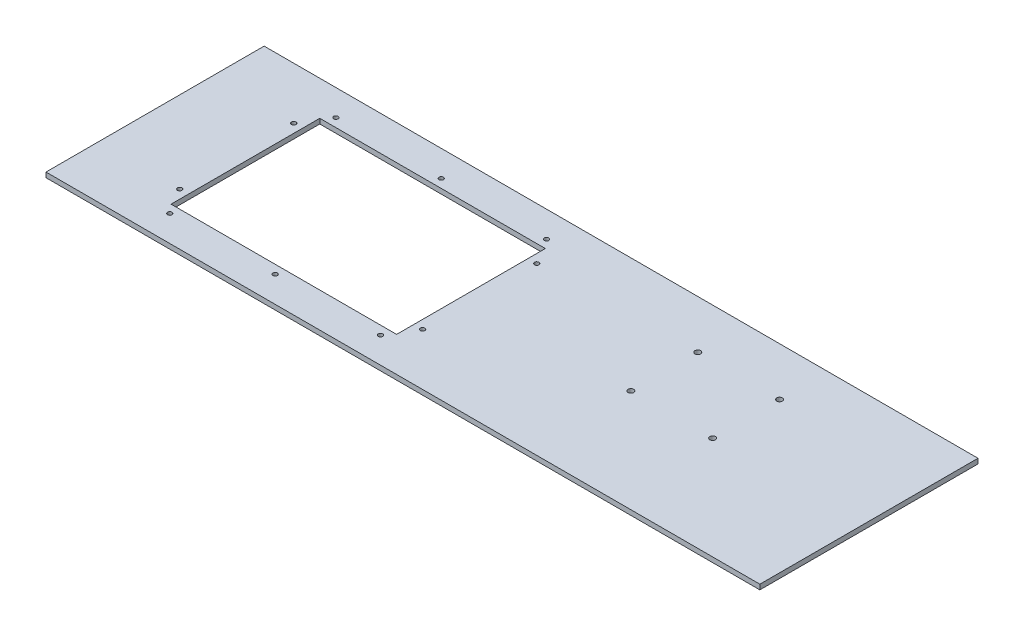
SolidWorks part; units mm, degrees
ref_plane "Ön Düzlem" through (0, 0, 0) normal (0, 0, 1) x (1, 0, 0)
ref_plane "Üst Düzlem" through (0, 0, 0) normal (0, 1, 0) x (1, 0, 0)
ref_plane "Sağ Düzlem" through (0, 0, 0) normal (1, 0, 0) x (0, 0, -1)
sketch "Çizim1" plane through (0, 0, 0) normal (0, 1, 0) x (1, 0, 0)
  line L1 (-720, -220) -> (720, -220)
  line L2 (-720, -220) -> (-720, 220)
  line L3 (-720, 220) -> (720, 220)
  line L4 (720, -220) -> (720, 220)
  line L5 (-720, -220) -> (720, 220) construction
  line L6 (-720, 220) -> (720, -220) construction
  point P0 (0, 0)
  dimension "D1" = 1440
  dimension "D2" = 440
base flange "Taban-Flanş1" sketch "Çizim1" thickness 10 reverse thickness direction no parameters "D1"=0.7366
sketch "Çizim2" plane through (0, -10, 0) normal (0, -1, 0) x (-1, 0, 0)
  line L0 (-720, 220) -> (720, 220) construction
  line L1 (537.75, 150) -> (82.75, 150)
  line L2 (537.75, 150) -> (537.75, -150)
  line L3 (537.75, -150) -> (82.75, -150)
  line L4 (82.75, 150) -> (82.75, -150)
  line L5 (720, 220) -> (720, -220) construction
  dimension "D1" = 70
  dimension "D2" = 182.25
  dimension "D3" = 300
  dimension "D4" = 455
extrude "Kes-Ekstrüzyon1" cut sketch "Çizim2" against normal blind 10 normal cut yes
sketch "Çizim3" plane through (0, -10, 0) normal (0, -1, 0) x (-1, 0, 0)
  line L0 (537.75, -150) -> (537.75, 150) construction
  line L1 (720, -220) -> (-720, -220) construction
  line L2 (82.75, -150) -> (537.75, -150) construction
  line L3 (82.75, 150) -> (82.75, -150) construction
  circle A0 centre (555.25, -115) radius 4.5
  circle A1 centre (522.75, -167.5) radius 4.5
  circle A2 centre (310.25, -167.5) radius 4.5
  circle A3 centre (97.75, -167.5) radius 4.5
  circle A4 centre (65.25, -115) radius 4.5
  dimension "D1" = 9
  dimension "D2" = 9
  dimension "D4" = 105
  dimension "D6" = 15
  dimension "D3" = 17.5
  dimension "D5" = 17.5
  dimension "D7" = 17.5
  dimension "D8" = 212.5
  dimension "D9" = 212.5
  dimension "D10" = 17.5
  dimension "D11" = 17.5
  dimension "D12" = 105
sketch "Çizim4" plane through (0, -10, 0) normal (0, -1, 0) x (-1, 0, 0)
  line L0 (537.75, -150) -> (537.75, 150) construction
  line L1 (82.75, -150) -> (537.75, -150) construction
  line L3 (82.75, 150) -> (82.75, -150) construction
  line L4 (720, -220) -> (-720, -220) construction
  line L5 (82.75, 0) -> (217.8041, 0) construction
  circle A0 centre (555.25, -115) radius 4.5
  circle A1 centre (522.75, -167.5) radius 4.5
  circle A2 centre (310.25, -167.5) radius 4.5
  circle A3 centre (97.75, -167.5) radius 4.5
  circle A4 centre (65.25, -115) radius 4.5
  circle A5 centre (65.25, 115) radius 4.5
  circle A6 centre (97.75, 167.5) radius 4.5
  circle A7 centre (310.25, 167.5) radius 4.5
  circle A8 centre (522.75, 167.5) radius 4.5
  circle A9 centre (555.25, 115) radius 4.5
  dimension "D1" = 9
  dimension "D2" = 17.5
  dimension "D3" = 35
  dimension "D4" = 17.5
  dimension "D5" = 15
  dimension "D6" = 17.5
  dimension "D7" = 212.5
  dimension "D8" = 17.5
  dimension "D9" = 212.5
  dimension "D10" = 17.5
  dimension "D11" = 105
extrude "Kes-Ekstrüzyon4" cut sketch "Çizim4" against normal blind 10 normal cut yes
sketch "Çizim5" plane through (0, 0, 0) normal (0, 1, 0) x (1, 0, 0)
  line L0 (720, 220) -> (-720, 220) construction
  line L1 (-720, -220) -> (720, -220) construction
  circle A0 centre (252.25, -12.5) radius 5.75
  circle A1 centre (252.25, 122.5) radius 5.75
  circle A2 centre (417.25, 122.5) radius 5.75
  circle A3 centre (417.25, -12.5) radius 5.75
  dimension "D1" = 11.5
  dimension "D2" = 165
  dimension "D3" = 97.5
  dimension "D4" = 207.5
  dimension "D5" = 165
extrude "Kes-Ekstrüzyon5" cut sketch "Çizim5" against normal blind 10 normal cut yes
sketch "Büküm-Çizgileri1" [suppressed] plane through (0, 0, 0) normal (0, 1, 0) x (1, 0, 0)
sketch "Sınırlandırma-Kutusu1" [suppressed] plane through (0, 0, 0) normal (0, 1, 0) x (1, 0, 0)
sheet metal parameters "Sac-Levha1" thickness 10 parameters "D1"=0.7366
flat pattern "Düz-Çoğaltma1" [suppressed]
sketch "Büküm-Çizgileri2" plane through (0, 0, 0) normal (0, 1, 0) x (1, 0, 0)
sketch3d "Sınırlandırma-Kutusu2" [suppressed]
  line L0 (-720, 220, 0) -> (720, 220, 0) construction
  line L1 (-720, -220, 0) -> (720, -220, 0) construction
  line L2 (-720, 220, 0) -> (-720, -220, 0) construction
  line L3 (720, 220, 0) -> (720, -220, 0) construction
sheet metal parameters "Sac-Levha2" thickness 10 parameters "D1"=0.7366
flat pattern "Düz-Çoğaltma1"
sketch "Büküm-Çizgileri2" plane through (0, 0, 0) normal (0, 1, 0) x (1, 0, 0)
sketch3d "Sınırlandırma-Kutusu2" [suppressed]
  line L0 (720, 220, 0) -> (-720, 220, 0) construction
  line L1 (720, -220, 0) -> (-720, -220, 0) construction
  line L2 (720, 220, 0) -> (720, -220, 0) construction
  line L3 (-720, 220, 0) -> (-720, -220, 0) construction
sheet metal parameters "Sac-Levha3" thickness 10 parameters "D1"=0.7366
flat pattern "Düz-Çoğaltma1" [suppressed]
sketch "Büküm-Çizgileri2" plane through (0, 0, 0) normal (0, 1, 0) x (1, 0, 0)
sketch3d "Sınırlandırma-Kutusu2" [suppressed]
  line L0 (720, 220, 0) -> (-720, 220, 0) construction
  line L1 (720, -220, 0) -> (-720, -220, 0) construction
  line L2 (720, 220, 0) -> (720, -220, 0) construction
  line L3 (-720, 220, 0) -> (-720, -220, 0) construction
sketch "Çizim3-1" [suppressed] plane through (0, -10, 0) normal (0, -1, 0) x (-1, 0, 0)
  line L0 (537.75, -150) -> (537.75, 150) construction
  line L1 (720, -220) -> (-720, -220) construction
  line L2 (82.75, -150) -> (537.75, -150) construction
  line L3 (82.75, 150) -> (82.75, -150) construction
  circle A0 centre (555.25, -115) radius 4.5
  circle A1 centre (522.75, -167.5) radius 4.5
  circle A2 centre (310.25, -167.5) radius 4.5
  circle A3 centre (97.75, -167.5) radius 4.5
  circle A4 centre (65.25, -115) radius 4.5
  dimension "D1" = 9
  dimension "D2" = 9
  dimension "D4" = 105
  dimension "D6" = 15
  dimension "D3" = 17.5
  dimension "D5" = 17.5
  dimension "D7" = 17.5
  dimension "D8" = 212.5
  dimension "D9" = 212.5
  dimension "D10" = 17.5
  dimension "D11" = 17.5
  dimension "D12" = 105
sheet metal parameters "Sac-Levha4" thickness 10 parameters "D1"=0.7366
flat pattern "Düz-Çoğaltma1" [suppressed]
sketch "Büküm-Çizgileri2" plane through (0, 0, 0) normal (0, 1, 0) x (1, 0, 0)
sketch3d "Sınırlandırma-Kutusu2" [suppressed]
  line L0 (720, 220, 0) -> (-720, 220, 0) construction
  line L1 (720, -220, 0) -> (-720, -220, 0) construction
  line L2 (720, 220, 0) -> (720, -220, 0) construction
  line L3 (-720, 220, 0) -> (-720, -220, 0) construction
sketch "Çizim3-1" [suppressed] plane through (0, -10, 0) normal (0, -1, 0) x (-1, 0, 0)
  line L0 (537.75, -150) -> (537.75, 150) construction
  line L1 (720, -220) -> (-720, -220) construction
  line L2 (82.75, -150) -> (537.75, -150) construction
  line L3 (82.75, 150) -> (82.75, -150) construction
  circle A0 centre (555.25, -115) radius 4.5
  circle A1 centre (522.75, -167.5) radius 4.5
  circle A2 centre (310.25, -167.5) radius 4.5
  circle A3 centre (97.75, -167.5) radius 4.5
  circle A4 centre (65.25, -115) radius 4.5
  dimension "D1" = 9
  dimension "D2" = 9
  dimension "D4" = 105
  dimension "D6" = 15
  dimension "D3" = 17.5
  dimension "D5" = 17.5
  dimension "D7" = 17.5
  dimension "D8" = 212.5
  dimension "D9" = 212.5
  dimension "D10" = 17.5
  dimension "D11" = 17.5
  dimension "D12" = 105
